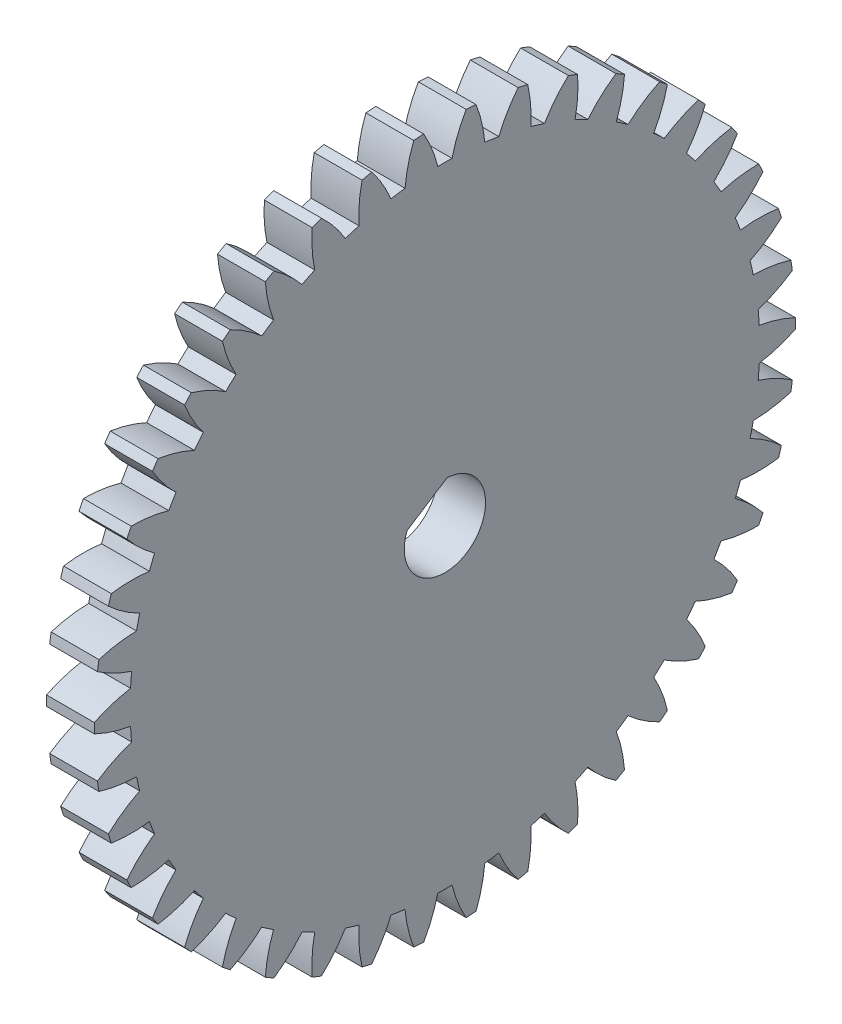
SolidWorks part; units mm, degrees
ref_plane "Plane1" through (0, 0, 0) normal (0, 0, 1) x (1, 0, 0)
ref_plane "Plane2" through (0, 0, 0) normal (0, 1, 0) x (1, 0, 0)
ref_plane "Plane3" through (0, 0, 0) normal (1, 0, 0) x (0, 0, -1)
sketch "HoldingSke" plane through (0, 0, 0) normal (0, 1, 0) x (1, 0, 0)
  line L0 (0, 0) -> (0.7431, -0.6691)
  line L1 (-15, 0) -> (100, 0) construction
  line L2 (0, 0) -> (-2.1039, 2.3779)
  line L3 (0, 0) -> (-11.863, 4.5341)
  line L4 (0, 0) -> (6.4178, 5.7786)
  line L5 (0, 0) -> (-46.8476, -17.4728)
  line L6 (0, 0) -> (-2.4869, -1.6779)
  line L7 (-2.1039, 2.3779) -> (8.6586, 51.2059)
  line L8 (-76.2, 54.61) -> (-76.1, 54.61)
  line L9 (-71.009, 38.7566) -> (-53.1078, 45.2721)
  line L10 (-76.2, 71.12) -> (104.1128, 71.12)
  line L11 (0, 0) -> (-3, 0)
  line L12 (-76.2, 101.6) -> (-76.162, 101.6)
  line L13 (24.9733, 27.94) -> (52.9518, 28.4284)
  line L14 (24.9733, 27.94) -> (24.9743, 27.94)
  line L15 (24.9733, 27.94) -> (100.4006, 29.5858)
  line L16 (-63.627, -1) -> (-12.827, -1)
  circle A0 centre (0, 0) radius 0.5
  circle A1 centre (0, 0) radius 19.749
  circle A2 centre (0, 0) radius 37.5
  circle A3 centre (0, 0) radius 0.5
  dimension "MHD" = 39.498
  dimension "Hub_dia" = 75
  dimension "Bore" = 1
  dimension "MBD" = 1
  dimension "Num_teeth" = 42
  dimension "Pitch" = 1
  dimension "Overall_len" = 50
  dimension "Show_teeth" = 42
  dimension "Thickness" = 3
  dimension "OAL" = 50.0001
  dimension "T_dim" = 0.1
  dimension "Ap" = 20
  dimension "H" = 19.05
  dimension "Pitch_radius" = 180.3128
  dimension "Width" = 3
  dimension "Backlash" = 0.038
  dimension "Addendum_fac" = 1
  dimension "Dedendum_fac" = 1.25
  dimension "Clearance_fac" = 0.25
  dimension "Dedendum_add" = 0.001
  dimension "Module" = 1
sketch "BasProSke" plane through (0, 0, 0) normal (0, 1, 0) x (1, 0, 0)
  line L0 (-10, 0) -> (60, 0) construction
  line L1 (0, 0) -> (0, 22)
  line L2 (0, 0) -> (3, 0)
  line L3 (3, 0) -> (3, 22)
  line L4 (3, 22) -> (0, 22)
  dimension "Thickness" = 3
  dimension "Diameter" = 44
revolve "Base-Revolve" add sketch "BasProSke" angle 360 about L0
sketch "TooCutSke" plane through (0, 0, 0) normal (1, 0, 0) x (0, 0, -1)
  line L1 (0, 0) -> (0, 107) construction
  line L2 (0, 0) -> (-0.8517, 20.9827) construction
  line L3 (0, 0) -> (-3.1368, 41.858) construction
  line L4 (-0.8517, 20.9827) -> (-1.5684, 20.929) construction
  arc A0 (0.4461, 19.744) -> (-0.4461, 19.744) centre (0, 0) ccw
  arc A1 (1.3487, 21.9841) -> (-1.3487, 21.9841) centre (0, 0) ccw
  circle A2 centre (0, 0) radius 21 construction
  circle A3 centre (0, 0) radius 19.7335 construction
  arc A4 (-0.4461, 19.744) -> (-1.3487, 21.9841) centre (-8.6078, 17.7572) ccw
  arc A5 (1.3487, 21.9841) -> (0.4461, 19.744) centre (8.6078, 17.7572) ccw
  dimension "Root_dia" = 39.498
  dimension "Overcut_dia" = 44.0508
  dimension "Pitch_dia" = 42
  dimension "Base_dia" = 39.4671
  dimension "Flank_rad" = 8.4
  dimension "Half_ang" = 4.286
  dimension "Half_CT" = 0.7187
extrude "ToothCut" cut sketch "TooCutSke" along normal through all
fillet "Breaks" [suppressed] radius 0.02 tangent propagation no
fillet "RootFillets" [suppressed] radius 0.251
pattern_circular "TeethCuts" count 42 every 8.571 about axis through (-10, 0, 0) along (1, 0, 0) of "ToothCut", "RootFillets", "Breaks"
sketch "HubNeaOneSke" plane through (0, 0, 0) normal (-1, 0, 0) x (0, 0, 1)
  circle A0 centre (0, 0) radius 19.749
  dimension "Diameter" = 39.498
extrude "HubNearOne" [suppressed] add sketch "HubNeaOneSke" along normal blind 47.0001
sketch "HubNeaBotSke" plane through (0, 0, 0) normal (-1, 0, 0) x (0, 0, 1)
  circle A0 centre (0, 0) radius 19.749
  dimension "Diameter" = 39.498
extrude "HubNearBoth" [suppressed] add sketch "HubNeaBotSke" along normal blind 23.5
ref_plane "FarPln" through (3, 0, 0) normal (1, 0, 0) x (0, 0, -1)
sketch "HubFarSke" plane through (3, 0, 0) normal (1, 0, 0) x (0, 0, -1)
  circle A0 centre (0, 0) radius 19.749
  dimension "Diameter" = 39.498
extrude "HubFar" [suppressed] add sketch "HubFarSke" along normal blind 23.5
sketch "BorSke" plane through (0, 0, 0) normal (1, 0, 0) x (0, 0, -1)
  line L0 (-2.38, 0.9154) -> (0.138, 2.5463)
  arc A0 (-2.38, 0.9154) -> (0.138, 2.5463) centre (0, 0) ccw
  dimension "D1" = 3
  dimension "D2" = 2.55
extrude "Bore" cut sketch "BorSke" along normal mid plane 100.0001
sketch "KeySke" plane through (0, 0, 0) normal (1, 0, 0) x (0, 0, -1)
  line L0 (-0.05, 0) -> (-0.05, 0.6)
  line L1 (-0.05, 0.6) -> (0.05, 0.6)
  line L2 (0.05, 0.6) -> (0.05, 0)
  line L3 (0, 0) -> (0, 34) construction
  line L4 (-0.05, 0) -> (0.05, 0)
  dimension "Offset" = 0.6
extrude "Keyway" [suppressed] cut sketch "KeySke" along normal mid plane 100.0001
pattern_circular "Keyway2" [suppressed] count 2 every 90 about axis through (-10, 0, 0) along (1, 0, 0) reverse direction yes
equation "' \"Module@HoldingSke\" = 6.35"
equation "' \"Num_teeth@HoldingSke\" = 12"
equation "' \"Ap@HoldingSke\" =  20"
equation "' \"Ap@HoldingSke\" = 20"
equation "' \"Width@HoldingSke\" = 0.5 * 25.4"
equation "' \"Hub_dia@HoldingSke\"= 1 * 25.4"
equation "' \"Hub_dia@HoldingSke\" = 1 * 25.4"
equation "' \"Overall_len@HoldingSke\" = 1.0 * 25.4"
equation "' \"Bore@HoldingSke\" = 0.75 * 25.4"
equation "' \"T_dim@HoldingSke\" = 0.1 * 25.4"
equation "' \"Width@KeySke\" = 0.25 * 25.4"
equation "' \"Show_teeth@HoldingSke\" = 13"
equation "' \"Backlash@HoldingSke\" = 0.009 * 25.4"
equation "' \"Addendum_fac@HoldingSke\" = 1.0"
equation "' \"Dedendum_fac@HoldingSke\" = 1.25"
equation "' \"Dedendum_add@HoldingSke\" = 0.00005 * 25.4"
equation "' \"Clearance_fac@HoldingSke\" = 0.25"
equation "\"Pitch@HoldingSke\" = 1 / \"Module@HoldingSke\""
equation "\"Overcut_dia@TooCutSke\" = (\"Num_teeth@HoldingSke\" + 2 * \"Addendum_fac@HoldingSke\") / \"Pitch@HoldingSke\" + 0.002 * 25.4"
equation "\"Pitch_dia@TooCutSke\" = \"Num_teeth@HoldingSke\" / \"Pitch@HoldingSke\""
equation "\"Base_dia@TooCutSke\" = \"Num_teeth@HoldingSke\" / \"Pitch@HoldingSke\" * cos((\"Ap@HoldingSke\"  * 3.14159265 / 180))"
equation "\"Root_dia@TooCutSke\" = (\"Num_teeth@HoldingSke\" + 2) / \"Pitch@HoldingSke\" - 2 * (\"Addendum_fac@HoldingSke\" + \"Dedendum_fac@HoldingSke\") / \"Pitch@HoldingSke\" - \"Dedendum_add@HoldingSke\" * 2"
equation "\"Half_ang@TooCutSke\" = 180 / \"Num_teeth@HoldingSke\""
equation "\"Half_CT@TooCutSke\" = \"Num_teeth@HoldingSke\" / \"Pitch@HoldingSke\" * sin((3.14159265 / 2 / \"Num_teeth@HoldingSke\")) / 2 - 7 * \"Backlash@HoldingSke\" / 4"
equation "\"Flank_rad@TooCutSke\" = \"Num_teeth@HoldingSke\" / \"Pitch@HoldingSke\" / 5"
equation "\"Radius@RootFillets\" = \"Clearance_fac@HoldingSke\" / \"Pitch@HoldingSke\" + \"Dedendum_add@HoldingSke\""
equation "\"Break_rad@Breaks\" = 0.02 / \"Pitch@HoldingSke\""
equation "\"Thickness@HoldingSke\" = \"Width@HoldingSke\""
equation "\"OAL@HoldingSke\" = \"Thickness@HoldingSke\""
equation "\"MHD@HoldingSke\" = (\"Num_teeth@HoldingSke\" + 2) / \"Pitch@HoldingSke\" - 2 * (\"Addendum_fac@HoldingSke\" + \"Dedendum_fac@HoldingSke\")  / \"Pitch@HoldingSke\" - \"Dedendum_add@HoldingSke\" * 2"
equation "\"MBD@HoldingSke\" = (\"Num_teeth@HoldingSke\" + 2) / \"Pitch@HoldingSke\" - 2 * (\"Addendum_fac@HoldingSke\" + \"Dedendum_fac@HoldingSke\")  / \"Pitch@HoldingSke\" - \"Dedendum_add@HoldingSke\" * 2 - 0.002 * 25.4"
equation "\"MHD@HoldingSke\" = ((sgn( \"MHD@HoldingSke\" - \"Hub_dia@HoldingSke\" )-1)*( \"MHD@HoldingSke\" - \"Hub_dia@HoldingSke\" ))/-2+ \"Hub_dia@HoldingSke\""
equation "\"MBD@HoldingSke\" = ((sgn( \"MBD@HoldingSke\" - \"Bore@HoldingSke\" )-1)*( \"MBD@HoldingSke\" - \"Bore@HoldingSke\" ))/-2+ \"Bore@HoldingSke\""
equation "\"OAL@HoldingSke\" = ((sgn( \"OAL@HoldingSke\" - \"Overall_len@HoldingSke\" )+1)*( \"OAL@HoldingSke\" - \"Overall_len@HoldingSke\" ))/2 + \"Overall_len@HoldingSke\" + 0.000002 * 25.4"
equation "\"Num_teeth@TeethCuts\" = int( \"Show_teeth@HoldingSke\" ) + 1"
equation "\"Num_teeth@TeethCuts\" = ((sgn( \"Num_teeth@TeethCuts\" - \"Num_teeth@HoldingSke\" )-1)*( \"Num_teeth@TeethCuts\" - \"Num_teeth@HoldingSke\" ))/-2+ \"Num_teeth@HoldingSke\""
equation "\"Num_teeth@TeethCuts\" = ((sgn( \"Num_teeth@TeethCuts\" - 2.0)+1)*( \"Num_teeth@TeethCuts\" - 2.0))/2 +2.0"
equation "\"Angle@TeethCuts\" = 360.0 / \"Num_teeth@HoldingSke\""
equation "\"Diameter@BasProSke\" = (\"Num_teeth@HoldingSke\" + 2 * \"Addendum_fac@HoldingSke\") / \"Pitch@HoldingSke\""
equation "\"Thickness@BasProSke\"  = \"Thickness@HoldingSke\""
equation "' \"Fillet_rad@BasProSke\" =  \"Thickness@HoldingSke\" * 0.05"
equation "' \"Fillet_rad@BasProSke\" = \"Thickness@HoldingSke\" * 0.05"
equation "\"MHD@HoldingSke\" = ((sgn( \"MHD@HoldingSke\" - \"Root_dia@TooCutSke\" )-1)*( \"MHD@HoldingSke\" - \"Root_dia@TooCutSke\" ))/-2+ \"Root_dia@TooCutSke\""
equation "\"Diameter@HubNeaOneSke\" = \"MHD@HoldingSke\""
equation "\"Length@HubNearOne\" = \"OAL@HoldingSke\" - \"Thickness@BasProSke\""
equation "\"Diameter@HubNeaBotSke\" = \"MHD@HoldingSke\""
equation "\"Length@HubNearBoth\" = ( \"OAL@HoldingSke\" - \"Thickness@BasProSke\" ) / 2.0"
equation "\"Thickness@FarPln\" = \"Thickness@BasProSke\""
equation "\"Diameter@HubFarSke\" = \"MHD@HoldingSke\""
equation "\"Length@HubFar\" = ( \"OAL@HoldingSke\" - \"Thickness@BasProSke\" ) / 2.0"
equation "\"D1@Bore\" = \"OAL@HoldingSke\" * 2.0"
equation "\"D1@Keyway\" = \"OAL@HoldingSke\" * 2.0"
equation "\"Offset@KeySke\" = \"T_dim@HoldingSke\" + \"MBD@HoldingSke\" / 2.0"
